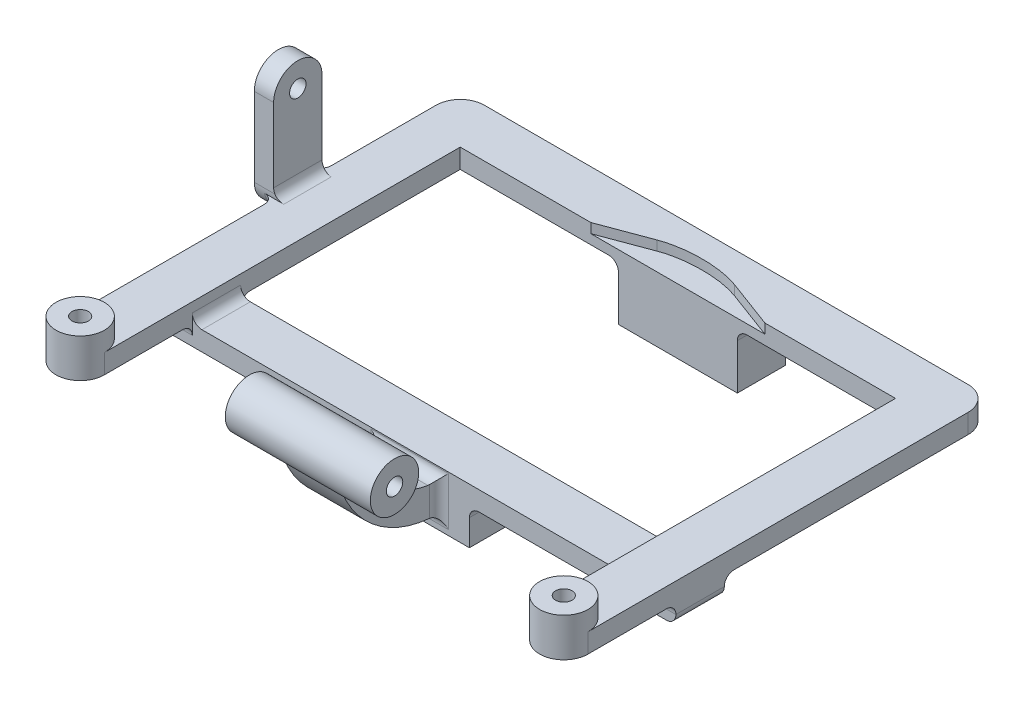
SolidWorks part; units mm, degrees
ref_plane "Plano frontal" through (0, 0, 0) normal (0, 0, 1) x (1, 0, 0)
ref_plane "Plano superior" through (0, 0, 0) normal (0, 1, 0) x (1, 0, 0)
ref_plane "Plano direito" through (0, 0, 0) normal (1, 0, 0) x (0, 0, -1)
sketch "Esboço1" plane through (0, 0, 0) normal (0, 1, 0) x (1, 0, 0)
  line L0 (-25, 0) -> (25, 0) construction
  line L1 (-25, 2.5) -> (25, 2.5)
  line L2 (-25, -2.5) -> (25, -2.5)
  arc A0 (-25, 2.5) -> (-25, -2.5) centre (-25, 0) ccw
  arc A1 (25, -2.5) -> (25, 2.5) centre (25, 0) ccw
  point P2 (0, 0)
  dimension "D1" = 50
  dimension "D2" = 5
extrude "Ressalto-extrusão1" add sketch "Esboço1" along normal blind 2
sketch "Esboço2" plane through (0, 0, 0) normal (0, 1, 0) x (1, 0, 0)
  line L0 (-25, -39.29) -> (-25, 0) construction
  line L1 (-27.5, -39.29) -> (-27.5, 0)
  line L2 (-22.5, -39.29) -> (-22.5, 0)
  arc A0 (-27.5, -39.29) -> (-22.5, -39.29) centre (-25, -39.29) ccw
  arc A1 (-22.5, 0) -> (-27.5, 0) centre (-25, 0) ccw
  arc A2 (-25, 2.5) -> (-25, -2.5) centre (-25, 0) ccw construction
  point P2 (-25, -19.645)
  dimension "D1" = 39.29
extrude "Ressalto-extrusão2" add sketch "Esboço2" along normal up to surface (2 mm away) up to face at (0, 2, 0)
sketch "Esboço9" plane through (0, 2, 0) normal (0, 1, 0) x (1, 0, 0)
  circle A0 centre (-25, -39.29) radius 2.5
  arc A1 (-27.5, -39.29) -> (-22.5, -39.29) centre (-25, -39.29) ccw construction
extrude "Ressalto-extrusão9" add sketch "Esboço9" along normal blind 2
sketch "Esboço3" plane through (0, 4, 0) normal (0, 1, 0) x (1, 0, 0)
  circle A0 centre (-25, -39.29) radius 0.85
  arc A1 (-22.5, -39.29) -> (-27.5, -39.29) centre (-25, -39.29) ccw construction
  dimension "D1" = 1.7
extrude "Corte-extrusão1" cut sketch "Esboço3" against normal through all
mirror "Espelhar1" about plane through (0, 0, 0) normal (1, 0, 0) of "Ressalto-extrusão9", "Corte-extrusão1", "Ressalto-extrusão2"
sketch "Esboço5" plane through (0, 0, 0) normal (0, -1, 0) x (1, 0, 0)
  line L0 (25, -2.5) -> (-25, -2.5) construction
  line L1 (-6.15, 2.5) -> (6.15, 2.5)
  line L2 (-6.15, 2.5) -> (-6.15, -2.5)
  line L3 (-6.15, -2.5) -> (6.15, -2.5)
  line L4 (6.15, 2.5) -> (6.15, -2.5)
  line L5 (-6.15, 2.5) -> (6.15, -2.5) construction
  line L6 (-6.15, -2.5) -> (6.15, 2.5) construction
  point P0 (0, 0)
  dimension "D1" = 12.3
extrude "Ressalto-extrusão3" add sketch "Esboço5" along normal blind 5.7
sketch "Esboço6" plane through (0, 0, 0) normal (1, 0, 0) x (0, 0, -1)
  line L1 (-25.2, 0) -> (-30.2, 0)
  line L2 (-25.2, 0) -> (-25.2, -2)
  line L3 (-25.2, -2) -> (-30.2, -2)
  line L4 (-30.2, 0) -> (-30.2, -2)
  line L6 (-2.5, -5.7) -> (-2.5, 0) construction
  line L8 (0, 0) -> (-39.29, 0) construction
  dimension "D1" = 5
  dimension "D2" = 22.7
  dimension "D3" = 2
extrude "Ressalto-extrusão7" add sketch "Esboço6" along normal mid plane 55
sketch "Esboço7" plane through (0, -2, 0) normal (0, -1, 0) x (1, 0, 0)
  line L0 (22.5, 25.2) -> (-22.5, 25.2) construction
  line L1 (-6.15, 25.2) -> (6.15, 25.2)
  line L2 (-6.15, 25.2) -> (-6.15, 30.2)
  line L3 (-6.15, 30.2) -> (6.15, 30.2)
  line L4 (6.15, 25.2) -> (6.15, 30.2)
  line L5 (22.5, 30.2) -> (-22.5, 30.2) construction
  point P8 (0, 25.2)
  dimension "D1" = 12.3
extrude "Ressalto-extrusão8" add sketch "Esboço7" along normal up to surface (3.7 mm away) up to face at (0, -5.7, 0)
sketch "Esboço16" plane through (0, -5.7, 0) normal (0, -1, 0) x (1, 0, 0)
  line L0 (-6.15, 25.2) -> (-27.5, 25.2) construction
  line L1 (42.1718, 13.85) -> (-35.0957, 13.85) construction
  line L2 (-22.5, 2.5) -> (-6.15, 2.5) construction
  circle A0 centre (0, 27.85) radius 1
  circle A1 centre (0, -0.15) radius 1
  dimension "D1" = 2
  dimension "D2" = 28
extrude "Corte-extrusão5" cut sketch "Esboço16" against normal up to surface (3.7 mm away) up to face at (-16.825, -2, 27.7)
sketch "Esboço8" plane through (0, 2, 0) normal (0, 1, 0) x (1, 0, 0)
  line L0 (-22.5, -2.5) -> (22.5, -2.5) construction
  line L1 (4, -0.6366) -> (9, -2.5)
  line L2 (9, -2.5) -> (4, -4.3634)
  line L3 (0, 7.9227) -> (0, -12.2146) construction
  line L4 (-9, -2.5) -> (-4, -4.3634)
  line L5 (-4, -0.6366) -> (-9, -2.5)
  ellipse E0 centre (0, -2.5) end of major axis (6, -2.5) minor radius 2.5 (-4, -4.3634) -> (4, -4.3634) ccw
  ellipse E1 centre (0, -2.5) end of major axis (6, -2.5) minor radius 2.5 (4, -0.6366) -> (-4, -0.6366) ccw
  dimension "D1" = 12
  dimension "D2" = 3
extrude "Corte-extrusão2" cut sketch "Esboço8" against normal blind 1
sketch "Esboço10" plane through (0, 0, 0) normal (1, 0, 0) x (0, 0, -1)
  line L0 (-39.29, 12.5849) -> (-39.29, -9.5265) construction
  line L1 (-41.79, 4) -> (-41.79, 0) construction
  line L2 (-36.79, 2) -> (-36.79, 4) construction
  line L4 (-36.79, 4) -> (-41.79, 4) construction
  circle A0 centre (-39.29, 5) radius 2.5
  dimension "D1" = 5
  dimension "D2" = 1
extrude "Ressalto-extrusão10" add sketch "Esboço10" along normal mid plane 15 separate body
sketch "Esboço11" plane through (0, 0, 0) normal (1, 0, 0) x (0, 0, -1)
  line L1 (-30.2, 0) -> (-30.2, -2) construction
  line L2 (-25.2, -5.7) -> (-30.2, -5.7) construction
  line L3 (-30.2, -1.2) -> (-30.2, -4.2)
  line L4 (-40.7696, 4.7533) -> (-37.8104, 5.2467)
  arc A0 (-39.29, 5) -> (-30.2, -2.7) centre (-30.2, 6.5155) ccw construction
  arc A1 (-40.7696, 4.7533) -> (-30.2, -4.2) centre (-30.2, 6.5155) ccw
  arc A2 (-37.8104, 5.2467) -> (-30.2, -1.2) centre (-30.2, 6.5155) ccw
  dimension "D1" = 3
  dimension "D2" = 1.5
  dimension "D3" = 1.5
extrude "Ressalto-extrusão11" add sketch "Esboço11" along normal mid plane 6
sketch "Esboço12" plane through (7.5, 0, 0) normal (1, 0, 0) x (0, 0, -1)
  circle A0 centre (-39.29, 5) radius 0.85
  circle A1 centre (-39.29, 5) radius 2.5 construction
  dimension "D1" = 1.7
extrude "Corte-extrusão3" cut sketch "Esboço12" against normal up to next
sketch "Esboço14" plane through (-27.5, 0, 0) normal (-1, 0, 0) x (0, 0, 1)
  line L0 (14.29, 10.64) -> (14.29, 2.5) construction
  line L1 (16.79, 10.64) -> (16.79, 2.5)
  line L2 (11.79, 10.64) -> (11.79, 2.5)
  line L3 (0, 0) -> (25.2, 0) construction
  arc A0 (16.79, 10.64) -> (11.79, 10.64) centre (14.29, 10.64) ccw
  arc A1 (11.79, 2.5) -> (16.79, 2.5) centre (14.29, 2.5) ccw
  circle A2 centre (39.29, 5) radius 0.85 construction
  point P2 (14.29, 6.57)
  point P8 (39.29, 5)
  dimension "D1" = 5.64
  dimension "D2" = 25
  dimension "D3" = 5
extrude "Ressalto-extrusão12" add sketch "Esboço14" along normal blind 2
sketch "Esboço15" plane through (-27.5, 0, 0) normal (1, 0, 0) x (0, 0, -1)
  circle A0 centre (-14.29, 10.64) radius 0.85
  arc A1 (-11.79, 10.64) -> (-16.79, 10.64) centre (-14.29, 10.64) ccw construction
  dimension "D1" = 1.7
extrude "Corte-extrusão4" cut sketch "Esboço15" against normal up to next
fillet "Filete2" radius 1 12 edges at (6.15, 0, 0) (-6.15, 0, 0) (0, -1.2, 30.2) (0, -4.2, 30.2) (-6.15, -2, 27.7) (6.15, -2, 27.7) (22.5, 0, 27.7) (-22.5, 0, 27.7) (3, -2.7, 30.2) (-3, -2.7, 30.2) (-27.5, 0.5635, 15.8711) (-27.5, 0.5635, 12.7089)
fillet "Filete3" radius 1 7 edges at (-27.5, -2, 27.7) (27.5, -2, 27.7) (25, 0, 30.2) (25, 0, 25.2) (-25, 0, 25.2) (-25, 0, 30.2) (-27.5, 2, 14.29)
